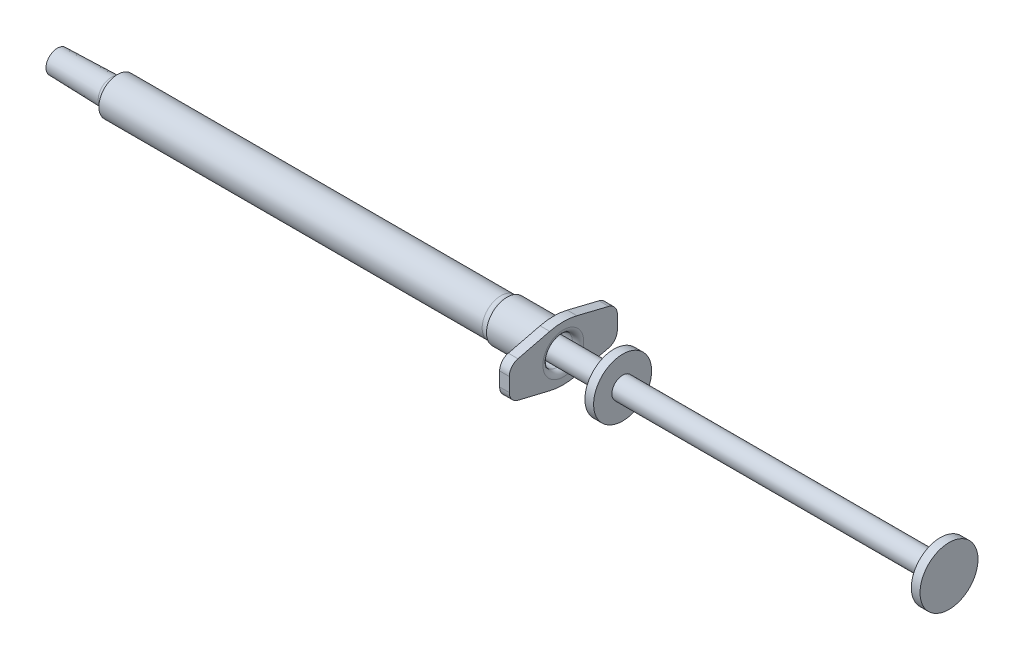
SolidWorks part; units mm, degrees
ref_plane "Front Plane" through (0, 0, 0) normal (0, 0, 1) x (1, 0, 0)
ref_plane "Top Plane" through (0, 0, 0) normal (0, 1, 0) x (1, 0, 0)
ref_plane "Right Plane" through (0, 0, 0) normal (1, 0, 0) x (0, 0, -1)
sketch "Sketch1" plane through (0, 0, 0) normal (0, 0, 1) x (1, 0, 0)
  line L0 (0, 2.5311) -> (132.0809, 2.5311) construction
  line L1 (0, 3.4111) -> (10, 3.4111)
  line L2 (0, 3.4111) -> (0, 4.5311)
  line L3 (0, 4.5311) -> (10, 4.8011)
  line L4 (10, 4.8011) -> (10.5922, 5.8311)
  line L5 (10.5922, 5.8311) -> (78.5922, 5.8311)
  line L6 (78.5922, 5.8311) -> (79.0781, 6.1461)
  line L7 (79.0781, 6.1461) -> (87.2781, 6.1461)
  line L8 (10, 3.4111) -> (10.5922, 3.7917)
  line L9 (10.5922, 3.7917) -> (10.9433, 5.1243)
  line L10 (10.9433, 5.1243) -> (87.2781, 5.1243)
  line L11 (87.2781, 5.1243) -> (87.2781, 6.1461)
  dimension "D1" = 10
  dimension "D2" = 0.88
  dimension "D3" = 2
  dimension "D4" = 3.3
  dimension "D5" = 2.27
  dimension "D6" = 68
  dimension "D7" = 3.615
  dimension "D8" = 8.2
revolve "Revolve2" add sketch "Sketch1" angle 360 about L0
sketch "Sketch2" plane through (0, 0, 0) normal (0, 0, 1) x (1, 0, 0)
  line L0 (10.5156, 2.5311) -> (11.1682, 5.0756)
  line L1 (11.1682, 5.0756) -> (16.3441, 5.0756)
  line L2 (16.3441, 5.0756) -> (16.5056, 4.4211)
  line L3 (16.5056, 4.4211) -> (97.8781, 4.4211)
  line L4 (97.8781, 4.4211) -> (97.8781, 7.6311)
  line L5 (87.2781, 5.1243) -> (87.2781, 6.1461) construction
  line L6 (0, 2.5311) -> (132.0809, 2.5311) construction
  line L7 (97.8781, 7.6311) -> (99.4081, 7.6311)
  line L8 (99.4081, 7.6311) -> (99.4081, 4.4211)
  line L9 (99.4081, 4.4211) -> (155.2781, 4.4211)
  line L10 (155.2781, 4.4211) -> (155.2781, 7.6311)
  line L11 (155.2781, 7.6311) -> (156.8081, 7.6311)
  line L12 (156.8081, 7.6311) -> (156.8081, 2.5311)
  line L13 (105.8866, 2.5311) -> (88.8229, 2.5311) construction
  line L14 (10.5156, 2.5311) -> (156.8081, 2.5311)
  dimension "D1" = 10.6
  dimension "D2" = 5.1
  dimension "D3" = 1.53
  dimension "D4" = 1.89
  dimension "D5" = 68
  dimension "D6" = 1.53
revolve "Revolve3" add sketch "Sketch2" angle 360 about L13
sketch "Sketch3" plane through (87.2781, 0, 0) normal (1, 0, 0) x (0, 0, -1)
  line L0 (-9.4994, 5.3266) -> (0, 7.6606)
  line L1 (9.4994, 5.3266) -> (0, 7.6606)
  line L2 (-9.4994, -0.2644) -> (-9.4994, 5.3266)
  line L3 (-9.4994, -0.2644) -> (-0.0441, -2.5394)
  line L4 (9.4994, -0.2644) -> (9.4994, 5.3266)
  line L5 (-9.4994, -0.2644) -> (9.4994, 5.3266) construction
  line L6 (-9.4994, 5.3266) -> (9.4994, -0.2644) construction
  line L7 (-0.0441, -2.5394) -> (9.4994, -0.2644)
  circle A0 centre (0, 2.5311) radius 2.5932
  point P0 (0, 2.5606)
  dimension "D1" = 5.1
  dimension "D2" = 5.1
extrude "Boss-Extrude1" add sketch "Sketch3" along normal blind 1.7
fillet "Fillet1" radius 10 2 edges at (88.1281, -2.5394, 0.0441) (88.1281, 7.6606, 0)
fillet "Fillet2" radius 2 5 edges at (78.5922, 2.5311, 3.3) (88.1281, -0.2644, 9.4994) (88.1281, 5.3266, 9.4994) (88.1281, -0.2644, -9.4994) (88.1281, 5.3266, -9.4994)
fillet "Fillet3" radius 1 3 edges at (87.2781, 2.5311, 3.615) (10, 2.5311, 2.27) (88.9781, 2.5311, -2.5932)
